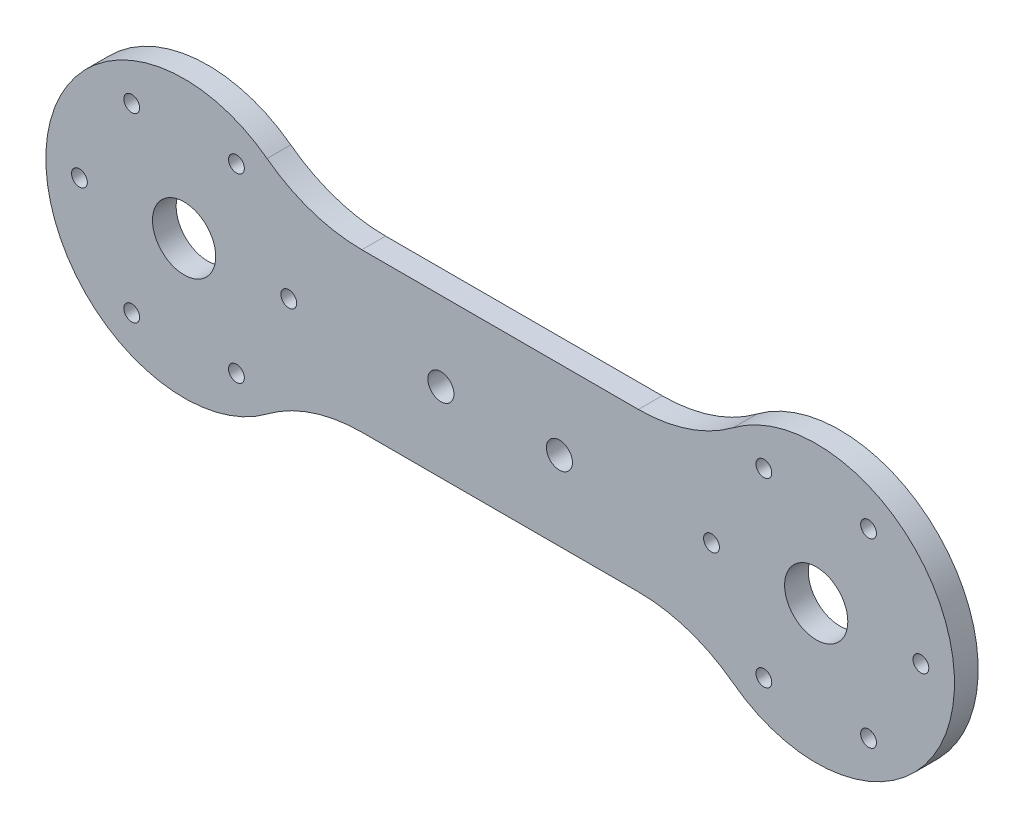
SolidWorks part; units mm, degrees
ref_plane "Plano frontal" through (0, 0, 0) normal (0, 0, 1) x (1, 0, 0)
ref_plane "Plano superior" through (0, 0, 0) normal (0, 1, 0) x (1, 0, 0)
ref_plane "Plano direito" through (0, 0, 0) normal (1, 0, 0) x (0, 0, -1)
sketch "Esboço1" plane through (0, 0, 0) normal (0, 0, 1) x (1, 0, 0)
  line L0 (14.3614, -10) -> (65.6386, -10)
  line L1 (0, 0) -> (80, 0) construction
  line L2 (14.3614, 10) -> (65.6386, 10)
  line L3 (0, 10) -> (80, 10) construction
  line L4 (0, -10) -> (80, -10) construction
  line L5 (40, 10) -> (40, -10) construction
  line L7 (0, 0) -> (80, 0) construction
  circle A0 centre (0, 0) radius 4
  circle A1 centre (-13.25, 0) radius 1
  circle A2 centre (0, 0) radius 4
  arc A3 (14.3614, 10) -> (14.3614, -10) centre (0, 0) ccw
  circle A4 centre (-6.625, 11.4748) radius 1
  circle A5 centre (0, 0) radius 4
  circle A6 centre (86.625, -11.4748) radius 1
  circle A7 centre (6.625, 11.4748) radius 1
  circle A8 centre (0, 0) radius 4
  circle A9 centre (80, 0) radius 4
  circle A10 centre (13.25, 0) radius 1
  circle A11 centre (0, 0) radius 4
  circle A12 centre (6.625, -11.4748) radius 1
  circle A13 centre (0, 0) radius 4
  circle A14 centre (-6.625, -11.4748) radius 1
  circle A15 centre (73.375, -11.4748) radius 1
  circle A16 centre (80, 0) radius 4
  circle A17 centre (66.75, 0) radius 1
  circle A18 centre (80, 0) radius 4
  circle A19 centre (73.375, 11.4748) radius 1
  circle A20 centre (80, 0) radius 4
  circle A21 centre (86.625, 11.4748) radius 1
  arc A22 (65.6386, 10) -> (65.6386, -10) centre (80, 0) cw
  circle A23 centre (80, 0) radius 4
  circle A24 centre (93.25, 0) radius 1
  circle A25 centre (80, 0) radius 4
  circle A26 centre (32.5, 0) radius 1.65
  circle A27 centre (47.5, 0) radius 1.65
  point P14 (40, 0)
  point P32 (0, 0)
  dimension "D1" = 8
  dimension "D3" = 2
  dimension "D4" = 13.25
  dimension "D6" = 6
  dimension "D8" = 35
  dimension "D9" = 3.3
  dimension "D2" = 10
  dimension "D5" = 10
  dimension "D7" = 40
  dimension "D10" = 15
  dimension "D11" = 32.5
extrude "Ressalto-extrusão1" add sketch "Esboço1" along normal blind 3 contours A22 L2 A3 L0 A21 A17 A9 A7 A0 A1 A4 A6 A10 A12 A14 A15 A19 A24 region at (40, 0, 0)
fillet "Filete1" radius 20 4 edges at (14.3614, -10, 1.5) (65.6386, -10, 1.5) (65.6386, 10, 1.5) (14.3614, 10, 1.5)
